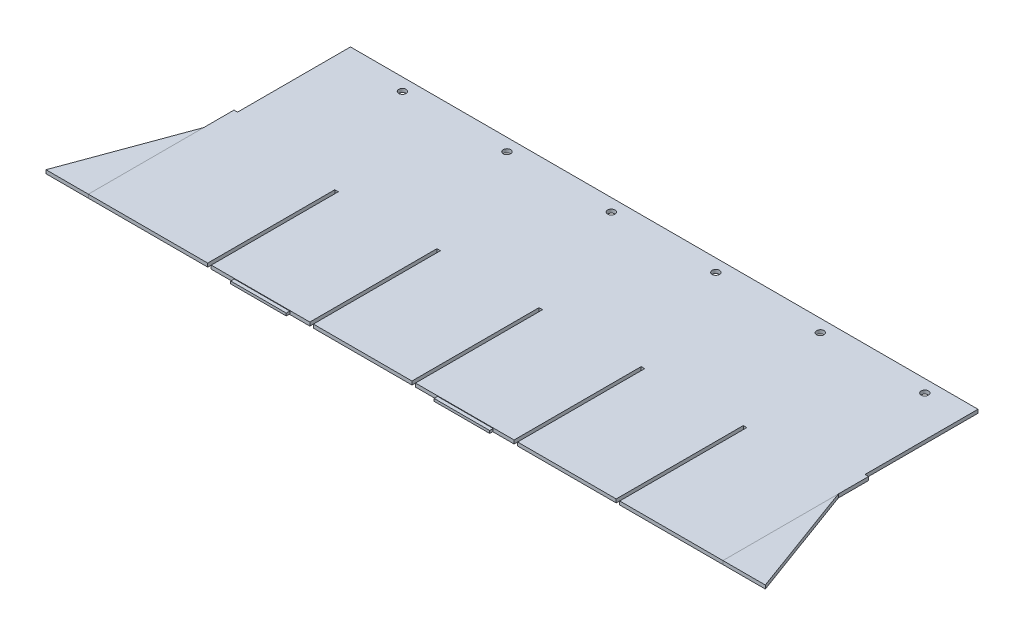
SolidWorks part; units mm, degrees
material "Custom Plastic"
ref_plane "X-Y Datum" through (0, 0, 0) normal (0, 0, 1) x (1, 0, 0)
ref_plane "X-Z Datum" through (0, 0, 0) normal (0, 1, 0) x (1, 0, 0)
ref_plane "Y-Z Datum" through (0, 0, 0) normal (1, 0, 0) x (0, 0, -1)
sketch "Sketch1" plane through (0, 0, 0) normal (0, 0, 1) x (1, 0, 0)
  line L1 (-285.4305, -1.5875) -> (285.4305, -1.5875)
  line L2 (-285.4305, -1.5875) -> (-285.4305, 1.5875)
  line L3 (-285.4305, 1.5875) -> (285.4305, 1.5875)
  line L4 (285.4305, -1.5875) -> (285.4305, 1.5875)
  line L5 (-285.4305, -1.5875) -> (285.4305, 1.5875) construction
  line L6 (-285.4305, 1.5875) -> (285.4305, -1.5875) construction
  point P0 (0, 0)
  dimension "D1" = 570.861
  dimension "D2" = 3.175
extrude "Boss-Extrude1" add sketch "Sketch1" along normal blind 232.6
sketch "Sketch2" plane through (0, 1.5875, 0) normal (0, 1, 0) x (1, 0, 0)
  line L0 (-176.5505, -128.8578) -> (-285.4305, -128.8578) construction
  line L1 (-285.4305, -232.6) -> (-285.4305, 0) construction
  line L3 (285.4305, -232.6) -> (-285.4305, -232.6) construction
  line L4 (-178.0615, -232.6) -> (-174.8865, -232.6)
  line L6 (-178.0615, -118.3) -> (-174.8865, -118.3)
  line L8 (-178.0615, -232.6) -> (-174.8865, -232.6)
  line L9 (-178.0615, -232.6) -> (-178.0615, -118.3)
  line L10 (-178.0615, -118.3) -> (-174.8865, -118.3)
  line L11 (-174.8865, -232.6) -> (-174.8865, -118.3)
  line L17 (-178.0615, -118.3) -> (-174.8865, -118.3)
  line L32 (-285.4305, -232.6) -> (-323.5305, -232.6)
  line L33 (-323.5305, -232.6) -> (-285.4305, -128.8578)
  line L34 (285.4305, -232.6) -> (323.5305, -232.6)
  line L35 (323.5305, -232.6) -> (285.4305, -128.8578)
  line L36 (-285.4305, -128.8578) -> (-285.4305, -232.6)
  line L37 (285.4305, -128.8578) -> (285.4305, -232.6)
  line L38 (-285.4305, 0) -> (-282.2555, 0)
  line L39 (-285.4305, 0) -> (-285.4305, -101.6)
  line L40 (-285.4305, -101.6) -> (-282.2555, -101.6)
  line L41 (-282.2555, 0) -> (-282.2555, -101.6)
  line L42 (285.4305, 0) -> (282.2555, 0)
  line L43 (285.4305, 0) -> (285.4305, -101.6)
  line L44 (285.4305, -101.6) -> (282.2555, -101.6)
  line L45 (282.2555, 0) -> (282.2555, -101.6)
  line M3 (285.4305, 0) -> (-285.4305, 0)
  line M4 (-285.4305, 0) -> (-285.4305, -232.6)
  line M5 (-285.4305, -232.6) -> (285.4305, -232.6)
  line M6 (285.4305, -232.6) -> (285.4305, 0)
  dimension "D1" = 107.369
  dimension "D2" = 103.7422
  dimension "D3" = 3.175
  dimension "D5" = 38.1
  dimension "D6" = 3.175
  dimension "D7" = 101.6
  dimension "D4" = 114.3
  dimension "D8" = 3.175
  dimension "D9" = 101.6
  dimension "D10" = 103.7422
  dimension "D11" = 38.1
extrude "Cut-Extrude1" cut sketch "Sketch2" against normal blind 3.175 contours L11 L6 L9 M5 region at (-176.474, 1.5875, 175.45)
sketch "Sketch6" plane through (0, 0, 232.6) normal (0, 0, 1) x (1, 0, 0)
  line L14 (78.762, -1.143) -> (78.762, 1.143)
  line L15 (28.762, 1.143) -> (78.762, 1.143)
  line L16 (28.762, -1.143) -> (78.762, 1.143) construction
  line L17 (28.762, 1.143) -> (78.762, -1.143) construction
  line L18 (28.762, -1.143) -> (78.762, -1.143)
  line L19 (28.762, -1.143) -> (28.762, 1.143)
  line L20 (-104.238, -1.143) -> (-104.238, 1.143)
  line L21 (-154.238, 1.143) -> (-104.238, 1.143)
  line L22 (-154.238, -1.143) -> (-104.238, 1.143) construction
  line L23 (-154.238, 1.143) -> (-104.238, -1.143) construction
  line L24 (-154.238, -1.143) -> (-104.238, -1.143)
  line L25 (-154.238, -1.143) -> (-154.238, 1.143)
  point P6 (237.7325, 0)
  dimension "D2" = 50
sketch "Sketch7" plane through (0, -1.5875, 0) normal (0, -1, 0) x (-1, 0, 0)
  line L1 (-285.4305, -232.6) -> (-285.4305, 0) construction
  circle A2 centre (-245.6805, -11.2916) radius 3.302
  dimension "D1" = 39.75
  dimension "D2" = 6.604
extrude "Cut-Extrude4" cut sketch "Sketch7" against normal through all contours A2 region at (245.6805, -1.5875, 11.2916)
extrude "Boss-Extrude2" add sketch "Sketch6" along normal blind 3.175
pattern_linear "LPattern1" count 6 spacing 93.98 along (-1, 0, 0) of "Cut-Extrude4"
extrude "Boss-Extrude4" add sketch "Sketch2<3>" against normal blind 3.175 separate body contours L33 L32 M4 | L34 L35 M6 region at (-298.1305, 1.5875, 198.0193) region at (298.1305, 1.5875, 198.0193)
sketch "Sketch2<3>" plane through (0, 1.5875, 0) normal (0, 1, 0) x (1, 0, 0) same geometry as "Sketch2"
pattern_linear "LPattern2" count 5 spacing 91.866 along (1, 0, 0) of "Cut-Extrude1"
extrude "Cut-Extrude5" cut sketch "Sketch2<4>" against normal through all contours L41 L40 M3 M4 | L45 L44 M3 M6 region at (283.843, 1.5875, 50.8) region at (-283.843, 1.5875, 50.8)
sketch "Sketch2<4>" plane through (0, 1.5875, 0) normal (0, 1, 0) x (1, 0, 0) same geometry as "Sketch2"
sketch "Sketch8" plane through (0, -1.5875, 0) normal (0, -1, 0) x (1, 0, 0)
  line L0 (-282.2555, 0) -> (282.2555, 0) construction
  line L1 (255.4605, 0) -> (207.4496, 0)
  line L2 (256.429, 61.9588) -> (256.429, 211.5258)
  line L4 (208.4181, 61.9588) -> (208.4181, 211.5258)
  line L5 (256.429, 61.9588) -> (208.4181, 61.9588)
  line L6 (285.4305, 0) -> (285.4305, 101.6) construction
  line L8 (256.429, 136.7423) -> (208.4181, 136.7423) construction
  line L9 (211.4551, 100.0588) -> (251.4551, 100.0588) construction
  line L11 (251.4551, 120.0588) -> (211.4551, 120.0588) construction
  line L12 (251.4551, 120.0588) -> (251.4551, 80.0588) construction
  line L13 (251.4551, 80.0588) -> (211.4551, 80.0588) construction
  line L14 (211.4551, 120.0588) -> (211.4551, 80.0588) construction
  line L15 (231.4551, 120.0588) -> (231.4551, 80.0588) construction
  line L16 (231.4551, 100.0588) -> (217.2925, 85.9371) construction
  line L21 (223.1996, 120.0707) -> (211.467, 108.3719) construction
  line L22 (211.467, 108.3719) -> (211.4431, 91.8034)
  line L27 (211.4431, 91.8034) -> (223.1419, 80.0708) construction
  line L28 (223.1419, 80.0708) -> (239.7105, 80.0469)
  line L33 (239.7105, 80.0469) -> (251.4431, 91.7457) construction
  line L35 (251.4431, 91.7457) -> (251.467, 108.3142)
  line L38 (251.467, 108.3142) -> (239.7682, 120.0468) construction
  line L39 (239.7682, 120.0468) -> (223.1996, 120.0707)
  line L45 (217.2925, 85.9371) -> (211.4551, 80.0588) construction
  line L46 (231.4551, 100.0588) -> (217.3333, 114.2213) construction
  line L47 (217.3333, 114.2213) -> (211.4551, 120.0588) construction
  line L48 (231.4551, 138.1588) -> (231.4551, 135.3258) construction
  line L49 (231.4551, 100.0588) -> (245.6176, 114.1805) construction
  line L50 (245.6176, 114.1805) -> (251.4551, 120.0588) construction
  line L51 (231.4551, 100.0588) -> (245.5768, 85.8963) construction
  line L52 (245.5768, 85.8963) -> (251.4551, 80.0588) construction
  line L53 (245.5768, 187.5883) -> (251.4551, 193.4258) construction
  line L54 (231.4551, 173.4258) -> (245.5768, 187.5883) construction
  line L56 (245.6176, 159.3041) -> (251.4551, 153.4258) construction
  line L57 (231.4551, 173.4258) -> (245.6176, 159.3041) construction
  line L58 (217.3333, 159.2633) -> (211.4551, 153.4258) construction
  line L59 (231.4551, 173.4258) -> (217.3333, 159.2633) construction
  line L60 (217.2925, 187.5475) -> (211.4551, 193.4258) construction
  line L61 (251.467, 165.1704) -> (239.7682, 153.4378) construction
  line L62 (239.7105, 193.4377) -> (251.4431, 181.7389) construction
  line L63 (211.4431, 181.6812) -> (223.1419, 193.4138) construction
  line L64 (223.1996, 153.4139) -> (211.467, 165.1127) construction
  line L65 (231.4551, 173.4258) -> (217.2925, 187.5475) construction
  line L66 (231.4551, 153.4258) -> (231.4551, 193.4258) construction
  line L67 (211.4551, 153.4258) -> (211.4551, 193.4258) construction
  line L68 (251.4551, 193.4258) -> (211.4551, 193.4258) construction
  line L69 (251.4551, 153.4258) -> (251.4551, 193.4258) construction
  line L70 (251.4551, 153.4258) -> (211.4551, 153.4258) construction
  line L71 (211.4551, 173.4258) -> (251.4551, 173.4258) construction
  line L72 (239.7682, 153.4378) -> (223.1996, 153.4139)
  line L73 (251.4431, 181.7389) -> (251.467, 165.1704)
  line L74 (223.1419, 193.4138) -> (239.7105, 193.4377)
  line L75 (211.467, 165.1127) -> (211.4431, 181.6812)
  line L76 (256.429, 211.5258) -> (208.4181, 211.5258)
  circle A10 centre (231.4551, 100.0588) radius 20 construction
  circle A11 centre (214.3738, 82.9979) radius 2
  circle A12 centre (248.5159, 82.9775) radius 2
  circle A13 centre (214.3942, 117.14) radius 2
  circle A14 centre (248.5363, 117.1196) radius 2
  circle A15 centre (231.4551, 173.4258) radius 20 construction
  circle A16 centre (248.5363, 156.365) radius 2
  circle A17 centre (214.3942, 156.3446) radius 2
  circle A18 centre (248.5159, 190.5071) radius 2
  circle A19 centre (214.3738, 190.4867) radius 2
  dimension "D6" = 4
  dimension "D7" = 4
  dimension "D8" = 4
  dimension "D9" = 4
  dimension "D1" = 29.0015
  dimension "D2" = 48.0109
  dimension "D3" = 40
  dimension "D4" = 40
  dimension "D5" = 40
extrude "Cut-Extrude6" [suppressed] cut sketch "Sketch8" against normal blind 2.54 contours A13 | A12 | A19 | A18 | A17 | A16 | A14 | A11
pattern_linear "LPattern3" [suppressed] count 5 spacing 90.17 of bodies 133
sketch "Sketch10" plane through (0, -1.5875, 0) normal (0, -1, 0) x (1, 0, 0)
  circle A0 centre (254.7859, 104.6371) radius 2
  circle A1 centre (207.7149, 104.6371) radius 2
extrude "Cut-Extrude7" [suppressed] cut sketch "Sketch10" against normal through all
sketch "Sketch11" [suppressed] plane through (0, -1.5875, 0) normal (0, -1, 0) x (1, 0, 0)
  line L0 (-282.2555, 0) -> (-282.2555, 101.6) construction
  circle A0 centre (-230.0055, 11.2916) radius 3.302
  dimension "D1" = 52.25
